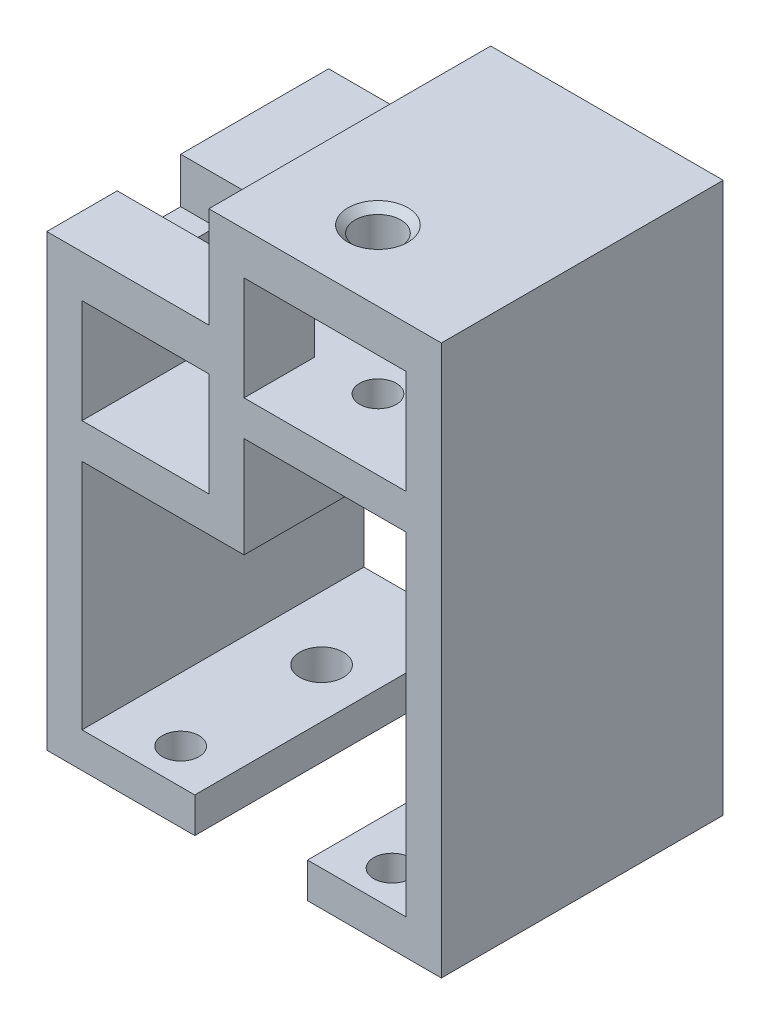
SolidWorks part; units mm, degrees
material "PET"
ref_plane "Front Plane" through (0, 0, 0) normal (0, 0, 1) x (1, 0, 0)
ref_plane "Top Plane" through (0, 0, 0) normal (0, 1, 0) x (1, 0, 0)
ref_plane "Right Plane" through (0, 0, 0) normal (1, 0, 0) x (0, 0, -1)
sketch "Sketch1" plane through (0, 0, 0) normal (0, 0, 1) x (1, 0, 0)
  line L0 (0, 0) -> (0, 63.75)
  line L1 (23, 78.05) -> (56, 78.05)
  line L2 (56, 78.05) -> (56, 0)
  line L3 (56, 0) -> (37, 0)
  line L4 (5, 5) -> (5, 38)
  line L6 (51, 72.05) -> (51, 57.3)
  line L7 (0, 63.75) -> (23, 63.75)
  line L9 (23, 57.75) -> (5, 57.75)
  line L10 (5, 43) -> (23, 43)
  line L11 (5, 5) -> (21, 5)
  line L12 (28, 38) -> (5, 38)
  line L13 (51, 57.3) -> (28, 57.3)
  line L14 (5, 43) -> (5, 57.75)
  line L15 (28, 52.3) -> (51, 52.3)
  line L17 (21, 5) -> (21, 0)
  line L18 (51, 52.3) -> (51, 5)
  line L19 (51, 5) -> (37, 5)
  line L20 (23, 63.75) -> (23, 57.75) construction
  line L21 (28, 57.3) -> (28, 72.05)
  line L22 (23, 63.75) -> (23, 78.05)
  line L23 (28, 72.05) -> (51, 72.05)
  line L24 (28, 52.3) -> (28, 38)
  line L25 (23, 57.75) -> (23, 43)
  line L26 (37, 5) -> (37, 0)
  line L27 (21, 0) -> (0, 0)
  point P20 (14, 43)
  point P22 (37, 57.3)
  dimension "D2" = 5
  dimension "D3" = 5
  dimension "D4" = 6
  dimension "D5" = 14.75
  dimension "D6" = 43
  dimension "D7" = 57.3
  dimension "D8" = 14.75
  dimension "D9" = 23
  dimension "D10" = 5
  dimension "D11" = 5
  dimension "D12" = 23
  dimension "D13" = 18
  dimension "D14" = 5
  dimension "D15" = 6
  dimension "D16" = 5
  dimension "D17" = 16
  dimension "D18" = 14
  dimension "D19" = 9
extrude "Boss-Extrude1" add sketch "Sketch1" along normal blind 40 contours L22 L7 L0 L3 L4 L12 L10 L14 L9 L15 L18 L2 L1 L21 L23 L6 L13 region at (0.9606, 31.875, 0)
sketch "Sketch2" plane through (0, 78.05, 0) normal (0, 1, 0) x (1, 0, 0)
  line L0 (23, -40) -> (56, -40) construction
  line L1 (56, -40) -> (56, 0) construction
  line L3 (0, 0) -> (23, 0) construction
  circle A0 centre (14, -15) radius 2.6
  circle A1 centre (37, -30) radius 2.6
  dimension "D1" = 23
  dimension "D2" = 5.2
  dimension "D3" = 5.2
  dimension "D4" = 19
  dimension "D5" = 10
  dimension "D6" = 15
extrude "Cut-Extrude1" cut sketch "Sketch2" against normal up to surface (40.05 mm away) up to face at (16.5, 38, 20)
sketch "Sketch3" plane through (28, 0, 0) normal (1, 0, 0) x (0, 0, -1)
  line L1 (-21, 72.05) -> (-30, 72.05)
  line L2 (-21, 72.05) -> (-21, 57.3)
  line L3 (-21, 57.3) -> (-30, 57.3)
  line L4 (-30, 72.05) -> (-30, 57.3)
  line L5 (0, 78.05) -> (0, 0) construction
  line L6 (-40, 72.05) -> (0, 72.05) construction
  dimension "D2" = 21
  dimension "D3" = 14.75
  dimension "D4" = 9
extrude "Cut-Extrude2" cut sketch "Sketch3" against normal up to next
sketch "Sketch4" plane through (5, 0, 0) normal (1, 0, 0) x (0, 0, -1)
  line L2 (-5, 43) -> (-5, 57.75)
  line L3 (-5, 57.75) -> (-15, 57.75)
  line L4 (-15, 43) -> (-15, 57.75)
  line L5 (0, 78.05) -> (0, 0) construction
  line L6 (-5, 43) -> (-15, 43)
  line L7 (-40, 43) -> (0, 43) construction
  dimension "D1" = 5
  dimension "D2" = 10
  dimension "D3" = 14.75
extrude "Cut-Extrude3" cut sketch "Sketch4" against normal through all
sketch "Sketch6" plane through (0, 78.05, 0) normal (0, 1, 0) x (1, 0, 0)
  circle A0 centre (14, -15) radius 3.25
  circle A1 centre (37, -30) radius 3.25
  dimension "D1" = 6.5
  dimension "D2" = 6.5
extrude "Cut-Extrude4" cut sketch "Sketch6" against normal up to next
ref_axis "Axis1" through (37, 72.05, 30) along (0, 1, 0)
ref_plane "Plane1" through (37, 0, 0) normal (1, 0, 0) x (0, 0, -1)
chamfer "Chamfer1" distance 1 angle 45 2 edges at (37, 78.05, 33.25) (14, 63.75, 18.25)
sketch "Sketch7" plane through (0, 0, 0) normal (0, -1, 0) x (1, 0, 0)
  line L0 (14, 40) -> (14, 0) construction
  line L1 (21, 40) -> (0, 40) construction
  line L2 (21, 0) -> (0, 0) construction
  line L3 (44, 40) -> (44, 0) construction
  line L4 (56, 40) -> (37, 40) construction
  line L5 (0, 40) -> (0, 0) construction
  line L6 (56, 40) -> (56, 0) construction
  line L7 (0, 15) -> (56, 15) construction
  line L8 (0, 35) -> (56, 35) construction
  circle A0 centre (14, 35) radius 2.6
  circle A1 centre (44, 35) radius 2.6
  circle A2 centre (14, 15) radius 3.1
  circle A3 centre (44, 15) radius 3.1
  dimension "D5" = 5.2
  dimension "D6" = 6.2
  dimension "D7" = 5.2
  dimension "D8" = 6.2
  dimension "D1" = 14
  dimension "D2" = 12
  dimension "D3" = 15
  dimension "D4" = 5
extrude "Cut-Extrude5" cut sketch "Sketch7" against normal up to next
